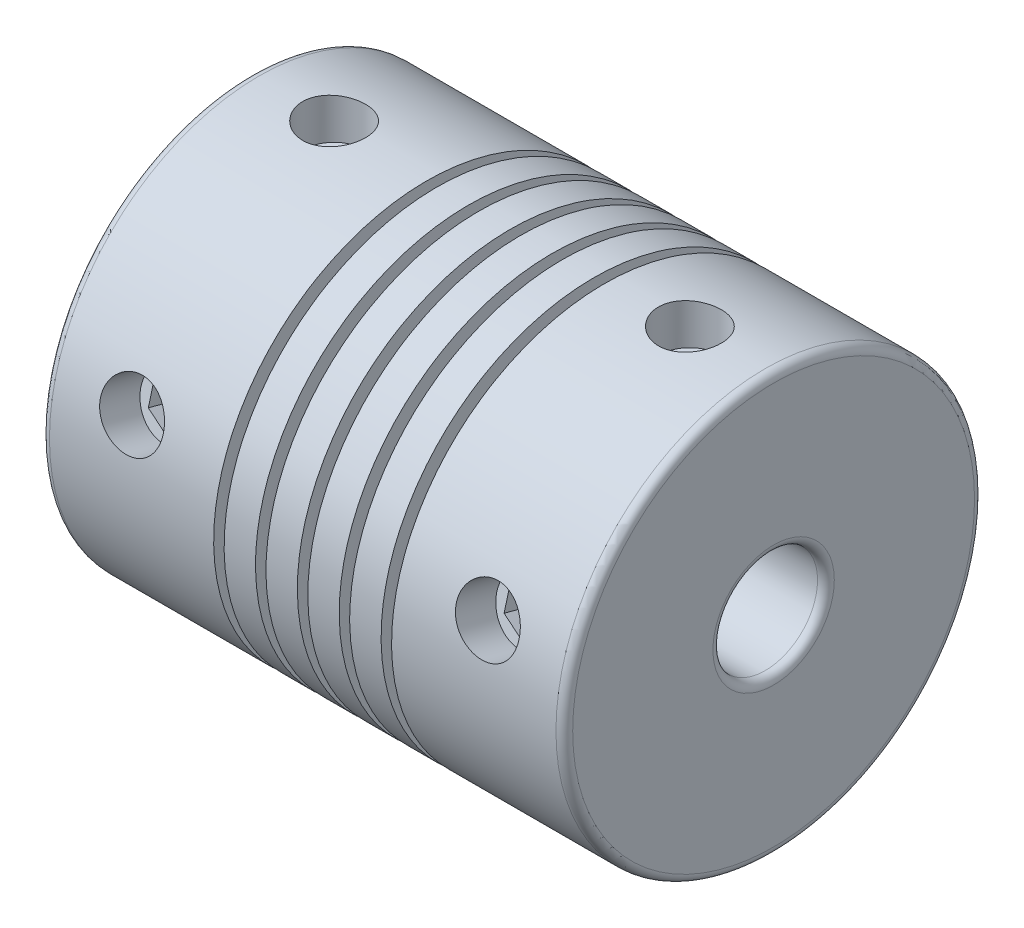
SolidWorks part; units mm, degrees
material "1060 Alloy"
ref_plane "Front Plane" through (0, 0, 0) normal (0, 0, 1) x (1, 0, 0)
ref_plane "Top Plane" through (0, 0, 0) normal (0, 1, 0) x (1, 0, 0)
ref_plane "Right Plane" through (0, 0, 0) normal (1, 0, 0) x (0, 0, -1)
sketch "Sketch1" plane through (0, 0, 0) normal (1, 0, 0) x (0, 0, -1)
  circle A0 centre (0, 0) radius 10
  circle A1 centre (0, 0) radius 2.5
  dimension "D1" = 20
  dimension "D2" = 5
extrude "Boss-Extrude1" add sketch "Sketch1" along normal blind 17.5 and the other way blind 7.5
sketch "Sketch2" plane through (0, 0, 0) normal (0, 1, 0) x (1, 0, 0)
  line L0 (5, 10) -> (5, -4.0374) construction
  line L1 (17.5, 10) -> (-7.5, 10) construction
  circle A0 centre (13.5, 0) radius 1.5
  circle A1 centre (-3.5, 0) radius 1.5
  dimension "D1" = 3
  dimension "D2" = 17
extrude "Cut-Extrude1" cut sketch "Sketch2" along normal up to next from offset 8
sketch "Sketch4" plane through (0, 8, 0) normal (0, 1, 0) x (1, 0, 0)
  line L0 (17.5, -10) -> (17.5, 10) construction
  line L1 (14.5, 0.5774) -> (13.5, 1.1547)
  line L2 (13.5, 1.1547) -> (12.5, 0.5774)
  line L3 (12.5, 0.5774) -> (12.5, -0.5774)
  line L4 (12.5, -0.5774) -> (13.5, -1.1547)
  line L5 (13.5, -1.1547) -> (14.5, -0.5774)
  line L6 (14.5, -0.5774) -> (14.5, 0.5774)
  line L7 (5, 10) -> (5, -10) construction
  line L8 (17.5, 10) -> (-7.5, 10) construction
  line L9 (-7.5, -10) -> (17.5, -10) construction
  line L10 (-4.5, -0.5774) -> (-4.5, 0.5774)
  line L11 (-3.5, -1.1547) -> (-4.5, -0.5774)
  line L12 (-2.5, -0.5774) -> (-3.5, -1.1547)
  line L13 (-2.5, 0.5774) -> (-2.5, -0.5774)
  line L14 (-3.5, 1.1547) -> (-2.5, 0.5774)
  line L15 (-4.5, 0.5774) -> (-3.5, 1.1547)
  circle A0 centre (13.5, 0) radius 1 construction
  circle A1 centre (-3.5, 0) radius 1 construction
  dimension "D1" = 2
extrude "Cut-Extrude2" cut sketch "Sketch4" against normal blind 1
pattern_circular "CirPattern1" count 2 over 75 about axis through (-7.5, 0, 0) along (1, 0, 0) of "Cut-Extrude1", "Cut-Extrude2"
sketch "Sketch5" plane through (0, 0, 0) normal (1, 0, 0) x (0, 0, -1)
  circle A0 centre (0, 0) radius 10 construction
  circle A1 centre (0, 0) radius 10
curve "Helix/Spiral1" pitch 2 height 10 radius 10 left hand yes centre (0, 0, 0) axis (1, 0, 0) start towards (0, 0, -1)
sketch "Sketch7" plane through (0, 0, 0) normal (0, 1, 0) x (1, 0, 0)
  line L0 (-0.25, 2.5) -> (-7.5, 2.5) construction
  line L1 (-0.25, 10) -> (0.25, 10)
  line L2 (-0.25, 10) -> (-0.25, 2.5)
  line L3 (-0.25, 2.5) -> (0.25, 2.5)
  line L4 (0.25, 10) -> (0.25, 2.5)
  point P4 (0, 10)
  dimension "D1" = 0.5
sweep "Cut-Sweep2" cut profiles "Sketch7" path "Helix/Spiral1" align with end faces yes
fillet "Fillet1" radius 0.4 4 edges at (-7.5, 0, -10) (-7.5, 0, -2.5) (17.5, 0, -2.5) (17.5, 0, -10)
